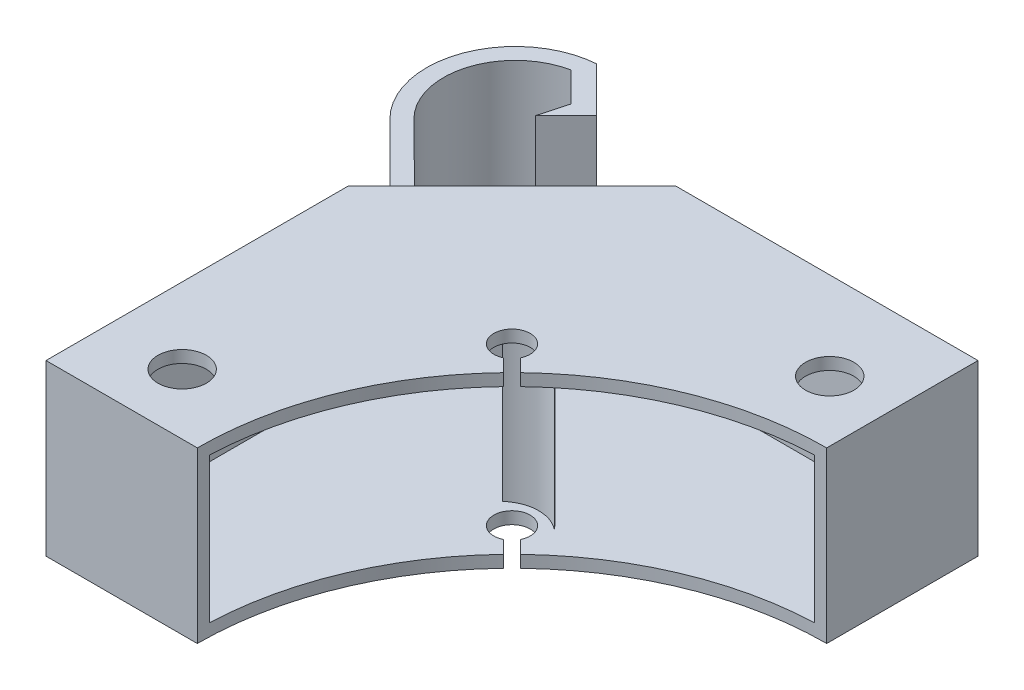
SolidWorks part; units mm, degrees
ref_plane "Front Plane" through (0, 0, 0) normal (0, 0, 1) x (1, 0, 0)
ref_plane "Top Plane" through (0, 0, 0) normal (0, 1, 0) x (1, 0, 0)
ref_plane "Right Plane" through (0, 0, 0) normal (1, 0, 0) x (0, 0, -1)
sketch "Sketch1" plane through (0, 0, 0) normal (0, 1, 0) x (1, 0, 0)
  line L0 (0, 0) -> (0, 50)
  line L1 (0, 0) -> (25, 0)
  line L2 (27, 77) -> (0, 50)
  line L3 (27, 77) -> (77, 77)
  line L4 (77, 77) -> (77, 52)
  line L5 (40.9444, 37.4699) -> (39.5301, 36.0556) construction
  line L6 (39.5301, 36.0556) -> (37.4088, 38.177)
  line L7 (40.9444, 37.4699) -> (38.823, 39.5912)
  line L8 (77, 52) -> (77, 0) construction
  line L9 (25, 0) -> (77, 0) construction
  arc A0 (39.5301, 36.0556) -> (25, 0) centre (77, 0) ccw
  arc A1 (40.9444, 37.4699) -> (77, 52) centre (77, 0) cw
  arc A2 (37.4088, 38.177) -> (38.823, 39.5912) centre (36.1159, 40.8841) cw
  point P13 (0, 0)
  point P14 (41.0724, 37.5926)
  point P15 (38.7879, 39.5574)
  dimension "D2" = 52
  dimension "D5" = 135
  dimension "D9" = 3
  dimension "D7" = 25
  dimension "D1" = 2
extrude "Boss-Extrude1" add sketch "Sketch1" along normal blind 28
shell "Shell1" thickness 2 removed face at (58.2678, 14, -46.4829) removed face at (30.5171, 14, -18.7322)
ref_plane "Plane3" through (0, 14, 0) normal (0, 1, 0) x (1, 0, 0)
sketch "Sketch7" plane through (0, 14, 0) normal (0, 1, 0) x (1, 0, 0)
  line L0 (0, 0) -> (0, 50)
  line L1 (0, 0) -> (25, 0)
  line L2 (25, 75) -> (0, 50)
  line L3 (25, 75) -> (75, 75)
  line L4 (75, 75) -> (75, 50)
  line L5 (40.431, 36.1246) -> (38.8754, 34.569) construction
  line L6 (38.8754, 34.569) -> (36.7541, 36.6903)
  line L7 (40.431, 36.1246) -> (38.3097, 38.2459)
  line L8 (75, 50) -> (75, 0) construction
  line L9 (25, 0) -> (75, 0) construction
  arc A0 (38.8754, 34.569) -> (25, 0) centre (75, 0) ccw
  arc A1 (40.431, 36.1246) -> (75, 50) centre (75, 0) cw
  arc A2 (36.7541, 36.6903) -> (38.3097, 38.2459) centre (36.1847, 38.8153) cw
  dimension "D5" = 135
  dimension "D2" = 50
  dimension "D11" = 2.2
  dimension "D6" = 2.2
  dimension "D7" = 25
  dimension "D9" = 3
sketch "Sketch9" plane through (0, 14, 0) normal (0, 1, 0) x (1, 0, 0)
  circle A0 centre (36.1847, 38.8153) radius 6.4
  dimension "D1" = 12.8
extrude "Cut-Extrude1" cut sketch "Sketch9" against normal blind 12 and the other way blind 12
ref_plane "Plane4" through (0, 28, 0) normal (0, 1, 0) x (1, 0, 0)
sketch "Sketch12" plane through (0, 28, 0) normal (0, 1, 0) x (1, 0, 0)
  line L2 (77, 52) -> (77, 77) construction
  line L5 (40.431, 36.1246) -> (38.8754, 34.569) construction
  line L8 (75, 50) -> (75, 0) construction
  line L9 (25, 0) -> (75, 0) construction
  line L10 (77, 62.5) -> (67, 62.5) construction
  line L11 (12.5, 0) -> (12.5, 10) construction
  circle A3 centre (67, 62.5) radius 4
  circle A4 centre (12.5, 10) radius 4
  dimension "D3" = 8
  dimension "D10" = 8
  dimension "D6" = 2.2
  dimension "D4" = 10
extrude "Cut-Extrude3" cut sketch "Sketch12" against normal blind 2
sketch "Sketch17" plane through (-25, 0, -25) normal (-0.7071, 0, -0.7071) x (-0.7071, 0, 0.7071)
  line L8 (-72.5391, 1) -> (-36.3553, 1)
  line L9 (-36.3553, 1) -> (-36.3553, 27)
  line L10 (-36.3553, 27) -> (-72.5391, 27)
  line L11 (-72.5391, 27) -> (-72.5391, 1)
  line L12 (-72.5391, 1) -> (-36.3553, 1)
  line L13 (-36.3553, 1) -> (-36.3553, 27)
  line L14 (-36.3553, 27) -> (-72.5391, 27)
  line L15 (-72.5391, 27) -> (-72.5391, 1)
  dimension "D1" = 1
extrude "Boss-Extrude2" add sketch "Sketch17" along normal blind 30 contours L14 L15 L12 L13
sketch "Sketch19" plane through (0, 27, 0) normal (0, 1, 0) x (1, 0, 0)
  line L0 (-7.1766, 64.0016) -> (3.4125, 53.4125)
  line L1 (0.7071, 50.7071) -> (26.2929, 76.2929) construction
  line L2 (2.0478, 88.9524) -> (9.449, 81.5512)
  line L3 (9.449, 81.5512) -> (4.4104, 76.5127)
  line L4 (4.4104, 76.5127) -> (5.671, 81.0865)
  line L5 (5.671, 81.0865) -> (0.8073, 85.9502)
  line L6 (-5.1535, 65.9471) -> (5.4457, 55.4457)
  line L7 (3.4125, 53.4125) -> (0.7071, 50.7071)
  line L8 (0.7071, 50.7071) -> (-20.5061, 71.9203)
  line L9 (-20.5061, 71.9203) -> (5.0797, 97.5061)
  line L10 (5.0797, 97.5061) -> (26.2929, 76.2929)
  line L11 (26.2929, 76.2929) -> (5.4457, 55.4457)
  arc A0 (-7.1766, 64.0016) -> (2.0478, 88.9524) centre (3.1764, 74.3546) cw
  arc A1 (-5.1535, 65.9471) -> (0.8073, 85.9502) centre (3.1764, 74.3546) cw
  point P11 (3.1764, 74.3546)
  dimension "D1" = 3
sketch "Sketch22" plane through (0, 27, 0) normal (0, 1, 0) x (1, 0, 0)
  line L0 (3.4125, 53.4125) -> (5.4457, 55.4457)
split line "Split Line2"
extrude "Cut-Extrude14" cut sketch "Sketch19<7>" against normal blind 30
sketch "Sketch19<7>" plane through (0, 27, 0) normal (0, 1, 0) x (1, 0, 0) same geometry as "Sketch19"
equation "\"innerRadius\"= 52mm"
equation "\"addedDimension\"= 25mm"
equation "\"D2@Sketch1\"=\"innerRadius\""
equation "\"thinConnectorWidth\"= 1.2mm"
equation "\"D9@Sketch1\"=\"thinConnectorLength\""
equation "\"thinConnectorLength\"= 3mm"
equation "\"connectorCircleRadius\"= 2.4mm"
equation "\"D7@Sketch1\"=\"addedDimension\""
equation "\"shellWidth\"= 2mm"
equation "\"D1@Shell1\"=\"shellWidth\""
equation "\"extrusionHeight\"= 28mm"
equation "\"D1@Boss-Extrude1\"=\"extrusionHeight\""
equation "\"D1@Sketch9\"=2*(\"connectorCircleRadius\"+\"thinConnectorLength\") + \"shellWidth\""
equation "\"D2@Cut-Extrude1\"=\"extrusionHeight\"/2 - \"shellWidth\""
equation "\"D1@Cut-Extrude1\"=\"extrusionHeight\"/2-\"shellWidth\""
equation "\"magnetHoleDiam\"= 26.5mm"
equation "\"throughHoleRadius\"= 4mm"
equation "\"D3@Sketch12\"=\"throughHoleRadius\"*2"
equation "\"D10@Sketch12\"=\"throughHoleRadius\"*2"
equation "\"throughHoleDistanceFromEdge\"= 10mm"
equation "\"D1@Cut-Extrude3\"=\"shellWidth\""
